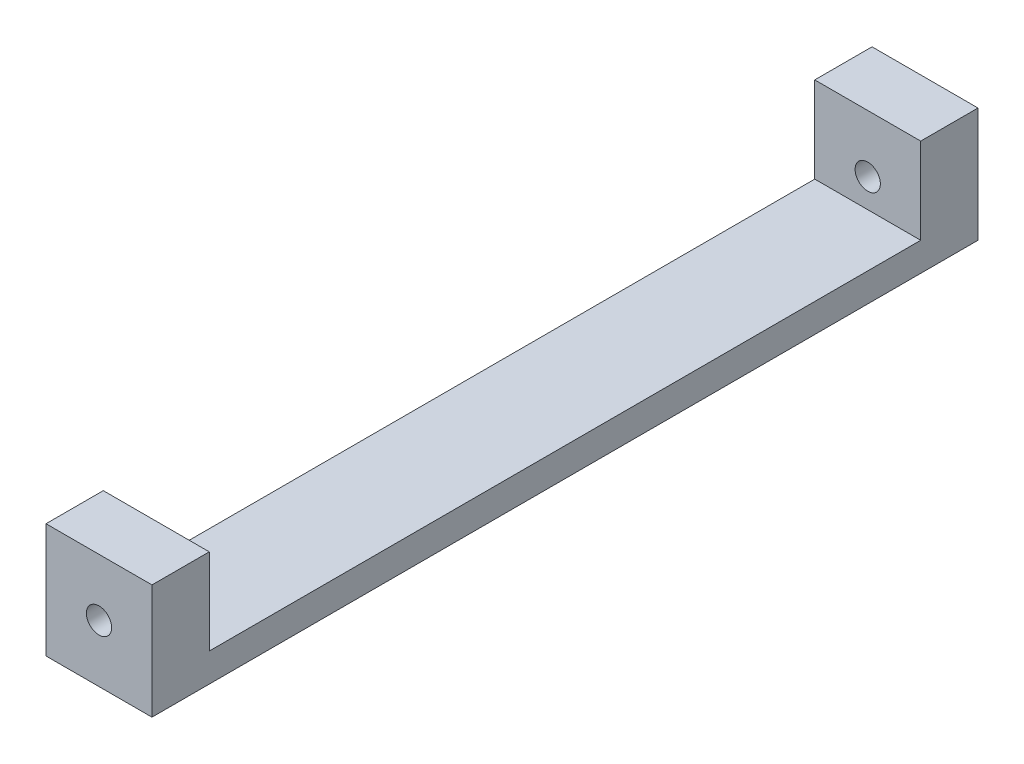
SolidWorks part; units mm, degrees
ref_plane "Front Plane" through (0, 0, 0) normal (0, 0, 1) x (1, 0, 0)
ref_plane "Top Plane" through (0, 0, 0) normal (0, 1, 0) x (1, 0, 0)
ref_plane "Right Plane" through (0, 0, 0) normal (1, 0, 0) x (0, 0, -1)
sketch "Sketch1" plane through (0, 0, 0) normal (0, 1, 0) x (1, 0, 0)
  line L1 (-5.8738, -45.7835) -> (5.8738, -45.7835)
  line L2 (-5.8738, -45.7835) -> (-5.8738, 45.7835)
  line L3 (-5.8738, 45.7835) -> (5.8738, 45.7835)
  line L4 (5.8738, -45.7835) -> (5.8738, 45.7835)
  line L5 (-5.8738, -45.7835) -> (5.8738, 45.7835) construction
  line L6 (-5.8738, 45.7835) -> (5.8738, -45.7835) construction
  point P0 (0, 0)
  point P6 (0, 0)
  dimension "D1" = 11.7475
  dimension "D2" = 91.567
extrude "Boss-Extrude1" add sketch "Sketch1" along normal blind 3.175
sketch "Sketch4" plane through (0, 0, 45.7835) normal (0, 0, 1) x (1, 0, 0)
  circle A0 centre (0, 6.35) radius 1.4
  dimension "D1" = 2.8
  dimension "D2" = 6.35
sketch "Sketch5" plane through (0, 0, 45.7835) normal (0, 0, 1) x (1, 0, 0)
  line L1 (-5.8738, 3.175) -> (5.8738, 3.175)
  line L2 (-5.8738, 3.175) -> (-5.8738, 12.7)
  line L3 (-5.8738, 12.7) -> (5.8738, 12.7)
  line L4 (5.8738, 3.175) -> (5.8738, 12.7)
  dimension "D1" = 9.525
extrude "Boss-Extrude2" add sketch "Sketch5" against normal blind 6.35
mirror "Mirror1" about plane through (0, 0, 0) normal (0, 0, 1) of "Boss-Extrude2"
extrude "Cut-Extrude1" cut sketch "Sketch4" against normal through all
equation "\"tighttol\" = 0.005in"
equation "\"normtol\" = 0.01in"
equation "\"loosetol\" = 0.02in"
equation "\"Fry height\"= 0.5in"
equation "\"Fry spacing\"= 0.5625in"
equation "\"Potato width\"= \"Fry spacing\" * 4"
equation "\"Potato length\"= 80mm"
equation "\"D1@Sketch1\"=\"Fry spacing\" - 5 * \"loosetol\""
equation "\"D2@Sketch1\"=3.625-\"loosetol\""
equation "\"D1@Sketch4\"=2.8mm"
